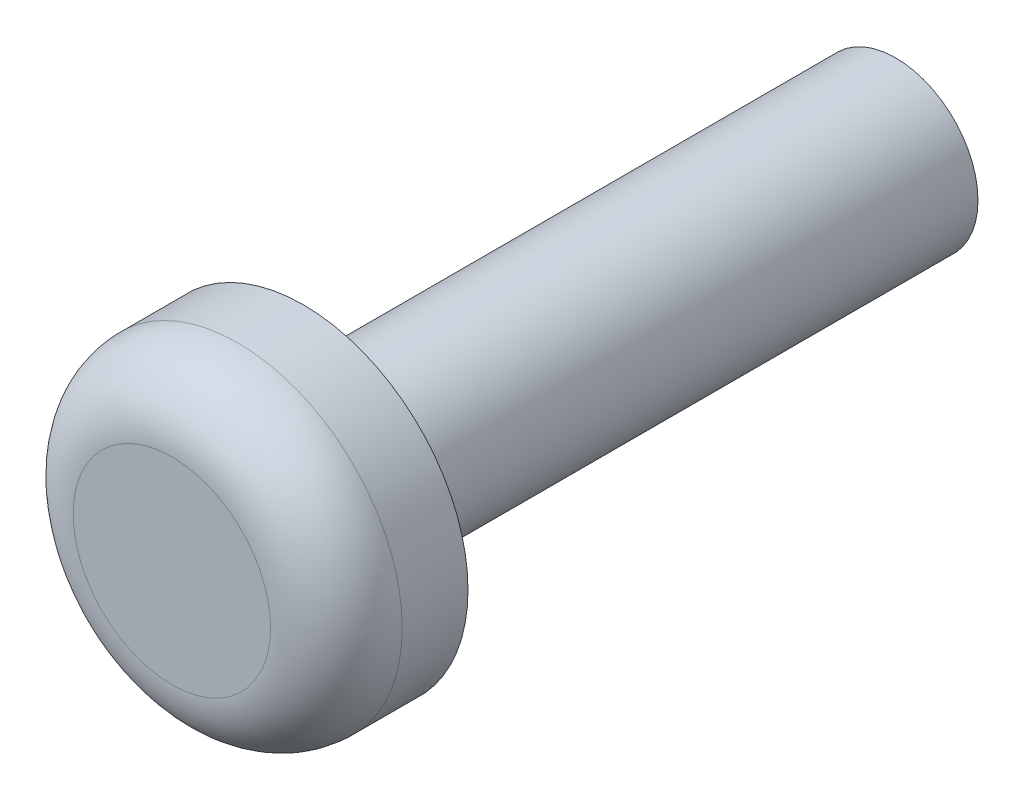
SolidWorks part; units mm, degrees
material "AISI 1045 Steel, cold drawn"
ref_plane "Front Plane" through (0, 0, 0) normal (0, 0, 1) x (1, 0, 0)
ref_plane "Top Plane" through (0, 0, 0) normal (0, 1, 0) x (1, 0, 0)
ref_plane "Right Plane" through (0, 0, 0) normal (1, 0, 0) x (0, 0, -1)
sketch "Sketch1" plane through (0, 0, 0) normal (0, 0, 1) x (1, 0, 0)
  circle A0 centre (0, 0) radius 1.25
  dimension "D1" = 2.5
extrude "Boss-Extrude1" add sketch "Sketch1" along normal blind 9
sketch "Sketch2" plane through (0, 0, 9) normal (0, 0, 1) x (1, 0, 0)
  circle A0 centre (0, 0) radius 2.5
extrude "Boss-Extrude2" add sketch "Sketch2" along normal blind 2
fillet "Fillet1" radius 1 1 edges at (2.5, 0, 11)
